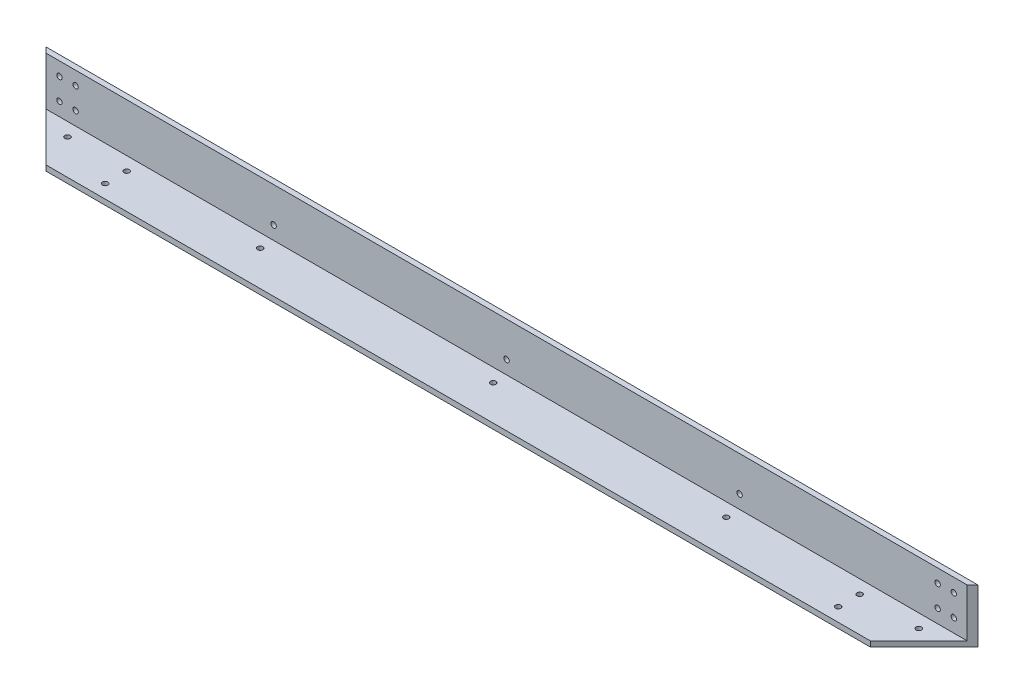
SolidWorks part; units mm, degrees
ref_plane "Front Plane" through (0, 0, 0) normal (0, 0, 1) x (1, 0, 0)
ref_plane "Top Plane" through (0, 0, 0) normal (0, 1, 0) x (1, 0, 0)
ref_plane "Right Plane" through (0, 0, 0) normal (1, 0, 0) x (0, 0, -1)
sketch "Sketch1" plane through (0, 0, 0) normal (1, 0, 0) x (0, 0, -1)
  line L0 (0, 0) -> (-31.75, 0)
  line L1 (-31.75, 0) -> (-31.75, 3.175)
  line L2 (-31.75, 3.175) -> (-3.175, 3.175)
  line L3 (-3.175, 3.175) -> (-3.175, 31.75)
  line L4 (-3.175, 31.75) -> (0, 31.75)
  line L5 (0, 31.75) -> (0, 0)
  dimension "LHeight" = 31.75
  dimension "LWidth" = 31.75
  dimension "LMaterialThickness" = 3.175
  dimension "D1" = 28.575
  dimension "D2" = 28.575
  dimension "D3" = 3.175
extrude "Boss-Extrude1" add sketch "Sketch1" along normal blind 550
chamfer "Chamfer6" distance 31.75 angle 45 1 edges at (550, 1.5875, 31.75)
chamfer "Chamfer7" distance 31.75 angle 45 1 edges at (0, 1.5875, 31.75)
sketch "TopHoles-Sketch3" plane through (0, 3.175, 0) normal (0, 1, 0) x (1, 0, 0)
  line L1 (518.25, -31.75) -> (31.75, -31.75) construction
  line L2 (550, 0) -> (0, 0) construction
  circle A5 centre (58.7375, -23.8125) radius 1.5875
  circle A6 centre (491.2625, -23.8125) radius 1.5875
  circle A9 centre (491.2625, -11.1125) radius 1.5875
  circle A10 centre (58.7375, -11.1125) radius 1.5875
  circle A11 centre (526.1875, -11.1125) radius 1.5875
  circle A12 centre (23.8125, -11.1125) radius 1.5875
  circle A13 centre (137.5, -11.1125) radius 1.5875
  circle A14 centre (275, -11.1125) radius 1.5875
  circle A15 centre (412.5, -11.1125) radius 1.5875
  dimension "D8" = 137.5
  dimension "D10" = 137.5
  dimension "D9" = 3.175
  dimension "D12" = 7.9375
  dimension "D2" = 11.1125
  dimension "D6" = 23.8125
  dimension "D3" = 23.8125
  dimension "D5" = 12.7
  dimension "D4" = 34.925
  dimension "D7" = 34.925
  dimension "D11" = 137.5
extrude "TopHoles-Cut-Extrude2" cut sketch "TopHoles-Sketch3" against normal through all
sketch "RightHoles-Sketch4" plane through (0, 0, 3.175) normal (0, 0, 1) x (1, 0, 0)
  line L0 (518.25, 0) -> (31.75, 0) construction
  line L3 (550, 31.75) -> (0, 31.75) construction
  line L4 (0, 0) -> (0, 31.75) construction
  line L5 (550, 0) -> (550, 31.75) construction
  circle A1 centre (11.1125, 23.8125) radius 1.5875
  circle A3 centre (529.3625, 23.8125) radius 1.5875
  circle A4 centre (20.6375, 23.8125) radius 1.5875
  circle A5 centre (538.8875, 23.8125) radius 1.5875
  circle A6 centre (11.1125, 11.1125) radius 1.5875
  circle A7 centre (20.6375, 11.1125) radius 1.5875
  circle A8 centre (529.3625, 11.1125) radius 1.5875
  circle A9 centre (538.8875, 11.1125) radius 1.5875
  circle A10 centre (137.5, 11.1125) radius 1.5875
  circle A11 centre (275, 11.1125) radius 1.5875
  circle A12 centre (412.5, 11.1125) radius 1.5875
  dimension "D2" = 3.175
  dimension "D4" = 7.9375
  dimension "D7" = 11.1125
  dimension "D1" = 11.1125
  dimension "D6" = 20.6375
  dimension "D3" = 11.1125
  dimension "D5" = 20.6375
  dimension "D8" = 137.5
  dimension "D9" = 137.5
  dimension "D10" = 137.5
extrude "RightHoles-Cut-Extrude3" cut sketch "RightHoles-Sketch4" against normal through all
equation "\"TopRailWidth\"= 1.25in"
equation "\"TopRailHeight\"= 1.25in"
equation "\"RailThickness\"= .125in'Spec"
equation "\"SideRailHoleY1FromEdge\"= \"HoleOffsetFromEdge\""
equation "\"SideRailHoleX1FromSide\"= \"HoleOffsetFromSide\""
equation "\"SideRailLength\"= 550mm"
equation "\"VSWidth\"= 1.25in'Spec"
equation "\"HoleOffsetFromEdge\"= \"RailThickness\" * 2.5"
equation "\"HoleOffsetFromSide\"= \"RailThickness\" * 3.5"
equation "\"TopHoleY1FromSide\"= \"HoleOffsetFromSide\""
equation "\"TopHoleX1FromEdge\"= \"TopCBWidth\" - \"HoleOffsetFromEdge\"'Equals 20.6375"
equation "\"TopCBWidth\"= \"TopRailWidth\" - \"RailThickness\"'Equals 28.575"
equation "\"SideRailHoleX2FromSide\"= \"VSWidth\" - \"HoleOffsetFromEdge\" - \"RailThickness\"'Equals 20.6375"
equation "\"FasteningHoleDiameter\"= .125in"
equation "\"SideRailHoleY2FromSide\"= \"HoleOffsetFromSide\""
equation "\"D2@RightHoles-Sketch4\"=\"FasteningHoleDiameter\""
equation "\"LWidth@Sketch1\"=\"TopRailWidth\""
equation "\"LHeight@Sketch1\"=\"TopRailHeight\""
equation "\"LMaterialThickness@Sketch1\"=\"RailThickness\""
equation "\"D1@Boss-Extrude1\"=\"SideRailLength\""
equation "\"D2@TopHoles-Sketch3\"=\"TopHoleY1FromSide\""
equation "\"D9@TopHoles-Sketch3\" = \"FasteningHoleDiameter\""
equation "\"D4@RightHoles-Sketch4\"=\"SideRailHoleY1FromEdge\""
equation "\"D1@Chamfer6\"=\"TopRailWidth\""
equation "\"D1@Chamfer7\"=\"TopRailWidth\""
equation "\"D7@RightHoles-Sketch4\"=\"SideRailHoleY2FromSide\""
equation "\"D1@RightHoles-Sketch4\"=\"SideRailHoleX1FromSide\""
equation "\"D6@RightHoles-Sketch4\"=\"SideRailHoleX2FromSide\""
equation "\"D3@RightHoles-Sketch4\"=\"SideRailHoleX1FromSide\""
equation "\"D5@RightHoles-Sketch4\"=\"SideRailHoleX2FromSide\""
equation "\"TopHoleX2FromX1\"= \"TopCBLength\" - \"TopHoleX1FromEdge\" - \"HoleOffsetFromEdge\"'Equals 34.925"
equation "\"TopHoleY2FromY1\"= \"TopCBWidth\" - \"TopHoleY1FromEdge\" - \"HoleOffsetFromEdge\"'Equals 12.7"
equation "\"D3@TopHoles-Sketch3\"=\"TopHoleX1FromEdge\" + \"RailThickness\""
equation "\"D6@TopHoles-Sketch3\"=\"TopHoleX1FromEdge\" + \"RailThickness\""
equation "\"D5@TopHoles-Sketch3\"=\"TopHoleY2FromY1\""
equation "\"TopCBLength\"= \"TopRailWidth\" * 2'Equals 63.5"
equation "\"TopHoleY1FromEdge\"= \"HoleOffsetFromEdge\""
equation "\"D4@TopHoles-Sketch3\"=\"TopHoleX2FromX1\""
equation "\"D7@TopHoles-Sketch3\"=\"TopHoleX2FromX1\""
equation "\"LeftOrRightEnclosureOffsets\"= \"SideRailLength\" / 4"
equation "\"D8@TopHoles-Sketch3\"=\"LeftOrRightEnclosureOffsets\""
equation "\"D10@TopHoles-Sketch3\"=\"LeftOrRightEnclosureOffsets\""
equation "\"D11@TopHoles-Sketch3\"=\"LeftOrRightEnclosureOffsets\""
equation "\"D8@RightHoles-Sketch4\"=\"LeftOrRightEnclosureOffsets\""
equation "\"D9@RightHoles-Sketch4\"=\"LeftOrRightEnclosureOffsets\""
equation "\"D10@RightHoles-Sketch4\"=\"LeftOrRightEnclosureOffsets\""
